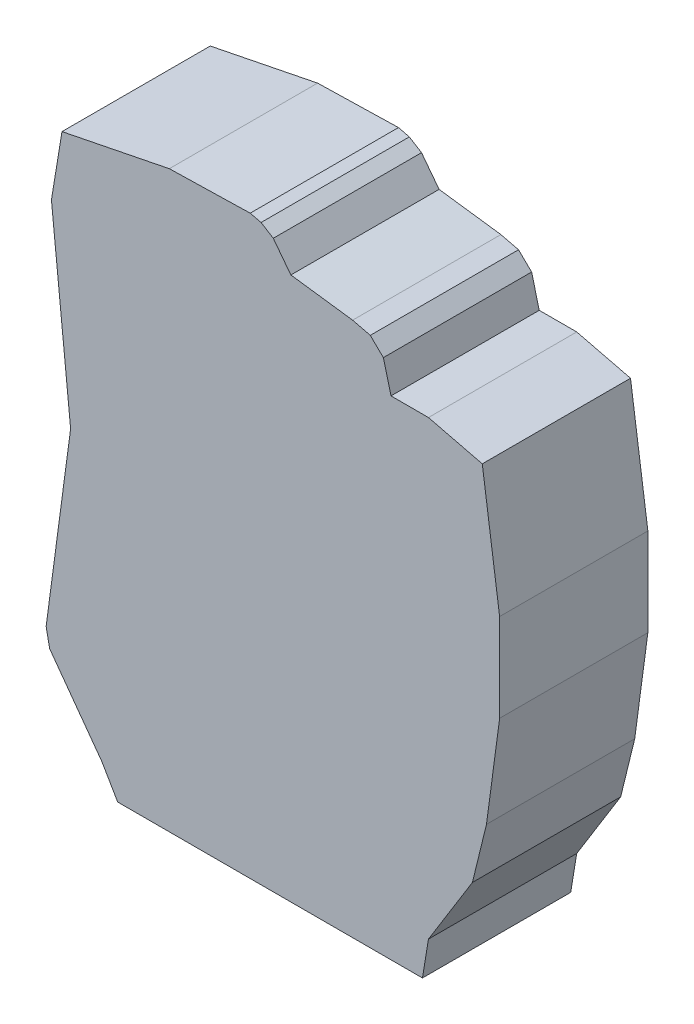
SolidWorks part; units mm, degrees
ref_plane "Front Plane" through (0, 0, 0) normal (0, 0, 1) x (1, 0, 0)
ref_plane "Top Plane" through (0, 0, 0) normal (0, 1, 0) x (1, 0, 0)
ref_plane "Right Plane" through (0, 0, 0) normal (1, 0, 0) x (0, 0, -1)
sketch "Sketch1" plane through (0, 0, 0) normal (0, 0, 1) x (1, 0, 0)
  line L0 (6.2196, 20.172) -> (31.0978, 20.172) construction
  line L16 (546.873, 9.9176) -> (893.0858, 9.9176) construction
  line L17 (543.5946, 13.7694) -> (705.2646, 13.7694) construction
  line L43 (547.2066, 9.9086) -> (608.8766, 9.9086) construction
  line L44 (546.5809, 9.8961) -> (608.2509, 9.8961)
  line L45 (608.2509, 9.8961) -> (609.4687, 17.3252)
  line L46 (609.4687, 17.3252) -> (618.3641, 31.6987)
  line L47 (618.3641, 31.6987) -> (621.2095, 43.3087)
  line L48 (621.2095, 43.3087) -> (623.8684, 63.2242)
  line L49 (623.8684, 63.2242) -> (623.8684, 81.0545)
  line L50 (623.8684, 81.0545) -> (620.3573, 106.0595)
  line L51 (620.3573, 106.0595) -> (609.4687, 108.7281)
  line L52 (609.4687, 108.7281) -> (601.8876, 108.7281)
  line L53 (601.8876, 108.7281) -> (600.3424, 114.6689)
  line L54 (600.3424, 114.6689) -> (597.6933, 117.2443)
  line L55 (597.6933, 117.2443) -> (594.1218, 118.1197)
  line L56 (594.1218, 118.1197) -> (581.6232, 119.7883)
  line L57 (581.6232, 119.7883) -> (578.0652, 124.4428)
  line L58 (578.0652, 124.4428) -> (575.593, 125.9728)
  line L59 (575.593, 125.9728) -> (573.398, 126.5107)
  line L60 (573.398, 126.5107) -> (557.03, 126.1181)
  line L61 (557.03, 126.1181) -> (535.3097, 121.7603)
  line L62 (535.3097, 121.7603) -> (533.8832, 113.0576)
  line L63 (533.8832, 113.0576) -> (533.1735, 108.7281)
  line L64 (533.1735, 108.7281) -> (536.3202, 77.7869)
  line L65 (536.3202, 77.7869) -> (537.0549, 70.5624)
  line L66 (537.0549, 70.5624) -> (532.0987, 33.4394)
  line L67 (532.0987, 33.4394) -> (532.8106, 29.8912)
  line L68 (532.8106, 29.8912) -> (543.389, 15.3737)
  line L69 (543.389, 15.3737) -> (546.5809, 9.8961)
  dimension "D1" = 61.67
  dimension "D2" = 61.67
extrude "Boss-Extrude1" add sketch "Sketch1" along normal blind 30
